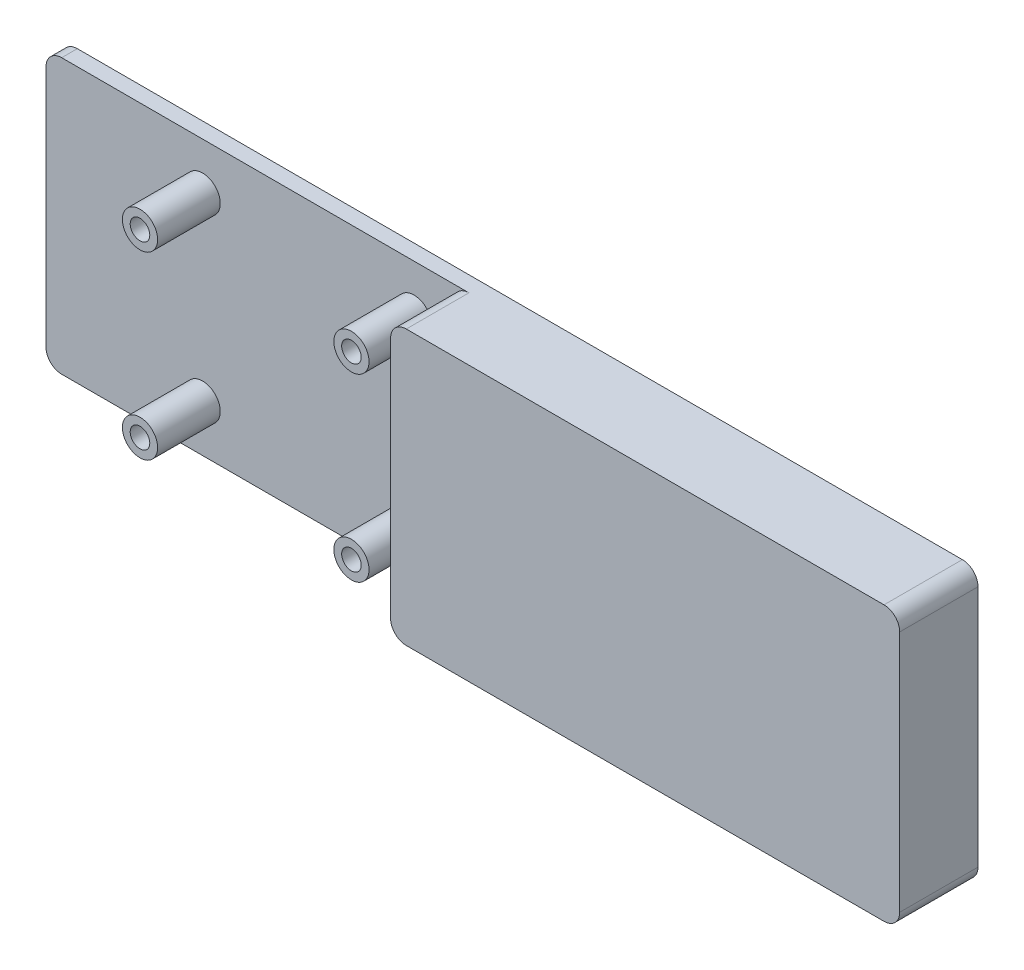
SolidWorks part; units mm, degrees
ref_plane "Front Plane" through (0, 0, 0) normal (0, 0, 1) x (1, 0, 0)
ref_plane "Top Plane" through (0, 0, 0) normal (0, 1, 0) x (1, 0, 0)
ref_plane "Right Plane" through (0, 0, 0) normal (1, 0, 0) x (0, 0, -1)
sketch "Sketch1" plane through (0, 0, 0) normal (0, 0, 1) x (1, 0, 0)
  line L0 (-6.5, 17.5) -> (-6.5, -17.5)
  line L1 (58.5, 17.5) -> (-58.5, 17.5)
  line L2 (58.5, 17.5) -> (58.5, -17.5)
  line L3 (58.5, -17.5) -> (-58.5, -17.5)
  line L4 (-58.5, 17.5) -> (-58.5, -17.5)
  line L5 (0, -17.5) -> (0, 17.5) construction
  line L6 (58.5, 0) -> (-58.5, 0) construction
  line L7 (-11.5, 11.5) -> (-38.5, 11.5) construction
  line L8 (-11.5, 11.5) -> (-11.5, -11.5) construction
  line L9 (-11.5, -11.5) -> (-38.5, -11.5) construction
  line L10 (-38.5, 11.5) -> (-38.5, -11.5) construction
  line L11 (-11.5, 11.5) -> (-38.5, -11.5) construction
  line L12 (-11.5, -11.5) -> (-38.5, 11.5) construction
  circle A0 centre (-38.5, 11.5) radius 1.25
  circle A1 centre (-11.5, 11.5) radius 1.25
  circle A2 centre (-11.5, -11.5) radius 1.25
  circle A3 centre (-38.5, -11.5) radius 1.25
  circle A4 centre (-38.5, 11.5) radius 2.25
  circle A5 centre (-38.5, -11.5) radius 2.25
  circle A6 centre (-11.5, -11.5) radius 2.25
  circle A7 centre (-11.5, 11.5) radius 2.25
  point P0 (0, 0)
  point P4 (-25, 0)
  dimension "D7" = 2.5
  dimension "D2" = 27
  dimension "D3" = 23
  dimension "D4" = 20
  dimension "D5" = 70
  dimension "D6" = 35
  dimension "D8" = 5
  dimension "D1" = 1
extrude "Boss-Extrude1" add sketch "Sketch1" along normal blind 10 contours A5 A3 | A6 A2 | A7 A1 | A4 A0 region at (-40.6864, 11.5, 0) region at (-40.6864, -11.5, 0) region at (-13.6864, -11.5, 0) region at (-13.6864, 11.5, 0)
extrude "Boss-Extrude2" add sketch "Sketch1<3>" along normal blind 2 contours L1 L4 L3 L2 A7 A6 A5 A4 | L3 L2 L1 L0 | L2 L1 L4 L3 region at (26, 0, 0) region at (-32.7717, 0, 0)
sketch "Sketch1<3>" plane through (0, 0, 0) normal (0, 0, 1) x (1, 0, 0) same geometry as "Sketch1"
extrude "Boss-Extrude3" add sketch "Sketch1<4>" along normal up to surface (10 mm away) contours L3 L2 L1 L0 region at (26, 0, 0) up to face at (-10.25, 11.5, 10)
sketch "Sketch1<4>" plane through (0, 0, 0) normal (0, 0, 1) x (1, 0, 0) same geometry as "Sketch1"
fillet "Fillet1" radius 2 6 edges at (58.5, 17.5, 5) (58.5, -17.5, 5) (-58.5, 17.5, 1) (-58.5, -17.5, 1) (-6.5, 17.5, 6) (-6.5, -17.5, 6)
